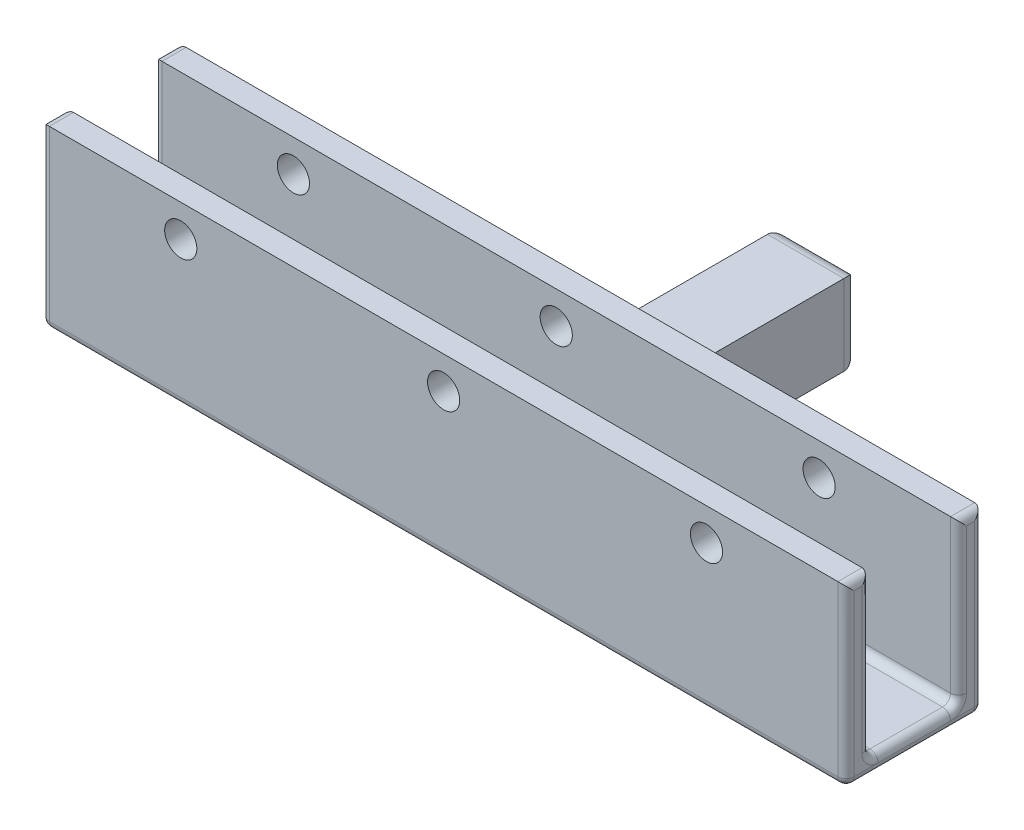
SolidWorks part; units mm, degrees
ref_plane "Front Plane" through (0, 0, 0) normal (0, 0, 1) x (1, 0, 0)
ref_plane "Top Plane" through (0, 0, 0) normal (0, 1, 0) x (1, 0, 0)
ref_plane "Right Plane" through (0, 0, 0) normal (1, 0, 0) x (0, 0, -1)
sketch "Sketch2" plane through (0, 0, 0) normal (0, 1, 0) x (1, 0, 0)
  line L1 (0, 0) -> (-100, 0)
  line L2 (0, 0) -> (0, -11)
  line L3 (0, -11) -> (-100, -11)
  line L4 (-100, 0) -> (-100, -11)
  line L5 (-100, -11) -> (0, -11)
  line L6 (-100, -11) -> (-100, -14)
  line L7 (-100, -14) -> (0, -14)
  line L8 (0, -11) -> (0, -14)
  line L9 (-100, 0) -> (0, 0)
  line L10 (-100, 0) -> (-100, 3)
  line L11 (-100, 3) -> (0, 3)
  line L12 (0, 0) -> (0, 3)
  dimension "D1" = 11
  dimension "D2" = 100
  dimension "D3" = 3
  dimension "D4" = 3
extrude "Boss-Extrude2" add sketch "Sketch2" along normal blind 2 contours L1 L12 L11 L10 | L1 L4 L3 L2 | L8 L3 L6 L7 region at (-50, 0, 5.5) region at (-50, 0, -1.5) region at (-50, 0, 12.5)
sketch "Sketch3" plane through (0, 2, 0) normal (0, 1, 0) x (1, 0, 0)
  line L1 (-100, 3) -> (0, 3)
  line L2 (-100, 3) -> (-100, -14)
  line L3 (-100, -14) -> (0, -14)
  line L4 (0, 3) -> (0, -14)
  line L5 (-100, 0) -> (0, 0)
  line L6 (-100, 0) -> (-100, -11)
  line L7 (-100, -11) -> (0, -11)
  line L8 (0, 0) -> (0, -11)
  line M5 (-100, 3) -> (-100, -14)
  line M6 (-100, -14) -> (0, -14)
  line M7 (0, -14) -> (0, 3)
  line M8 (0, 3) -> (-100, 3)
  dimension "D1" = 3
  dimension "D2" = 3
extrude "Boss-Extrude3" add sketch "Sketch3" along normal blind 20 contours L7 M5 M6 M7 | L5 L4 M5 M8 region at (-50, 2, -1.5) region at (-50, 2, 12.5)
ref_plane "Plane1" through (-50, 0, 0) normal (1, 0, 0) x (0, 0, -1)
fillet "Fillet2" radius 1 20 edges at (-100, 2, 5.5) (-100, 12, 11) (-100, 22, 12.5) (-100, 11, 14) (-100, 0, 5.5) (-100, 11, -3) (-100, 22, -1.5) (-100, 12, 0) (0, 11, -3) (0, 0, 5.5) (0, 11, 14) (0, 22, 12.5) (0, 12, 11) (0, 2, 5.5) (0, 12, 0) (0, 22, -1.5) (-50, 0, 14) (-50, 0, -3) (-50, 2, 0) (-50, 2, 11)
sketch "Sketch5" plane through (0, 0, -3) normal (0, 0, -1) x (-1, 0, 0)
  line L1 (45.25, 10) -> (54.75, 10)
  line L2 (45.25, 10) -> (45.25, 0)
  line L3 (45.25, 0) -> (54.75, 0)
  line L4 (54.75, 10) -> (54.75, 0)
  line L6 (50, 5.5) -> (50, -5.5) construction
  line L7 (1, 0) -> (99, 0) construction
  point P6 (50, 0)
  dimension "D1" = 9.5
  dimension "D2" = 10
extrude "Boss-Extrude5" add sketch "Sketch5" along normal blind 30 and the other way blind 1
fillet "Fillet3" radius 2 4 edges at (-50, 10, -33) (-54.75, 5, -33) (-50, 0, -33) (-45.25, 5, -33)
fillet "Fillet4" radius 2 4 edges at (-54.75, 0.2929, -2.7071) (-45.25, 0.2929, -2.7071) (-54.75, 5.5, -3) (-45.25, 5.5, -3)
sketch "Sketch6" plane through (0, 0, -3) normal (0, 0, -1) x (-1, 0, 0)
  line L0 (1, 22) -> (99, 22) construction
  line L1 (1, 22) -> (1, 1) construction
  circle A0 centre (17.3333, 18) radius 2
  circle A1 centre (50, 18) radius 2
  circle A2 centre (82.6667, 18) radius 2
  dimension "D2" = 4
  dimension "D1" = 4
  dimension "D3" = 16.3333
  dimension "D5" = 32.6667
  dimension "D4" = 3
extrude "Cut-Extrude1" cut sketch "Sketch6" against normal blind 39
sketch "Sketch7" plane through (0, 10, 0) normal (0, 1, 0) x (1, 0, 0)
  line L0 (-45.25, 31) -> (-54.75, 31) construction
  circle A0 centre (-50, 11) radius 2
  point P6 (-50, 31)
  dimension "D2" = 4
  dimension "D1" = 20
extrude "Cut-Extrude2" cut sketch "Sketch7" against normal blind 39
